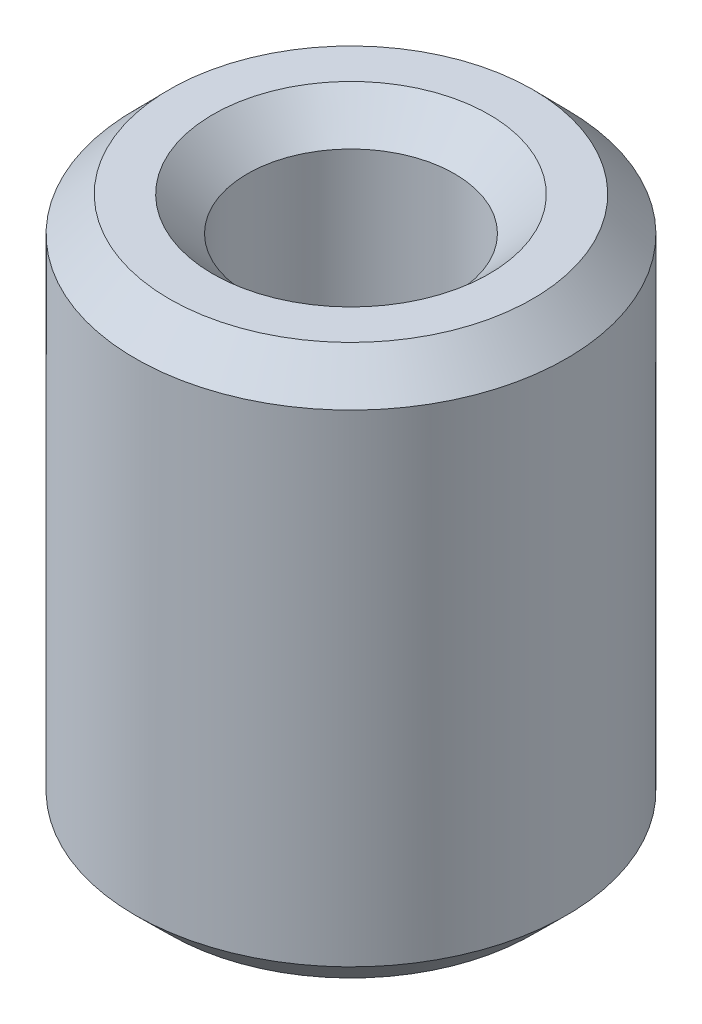
SolidWorks part; units mm, degrees
ref_plane "Front Plane" through (0, 0, 0) normal (0, 0, 1) x (1, 0, 0)
ref_plane "Top Plane" through (0, 0, 0) normal (0, 1, 0) x (1, 0, 0)
ref_plane "Right Plane" through (0, 0, 0) normal (1, 0, 0) x (0, 0, -1)
sketch "Sketch1" plane through (0, 0, 0) normal (0, 1, 0) x (1, 0, 0)
  circle A0 centre (0, 0) radius 7.5
  dimension "SLEEVE_OD" = 15
extrude "Boss-Extrude1" add sketch "Sketch1" along normal blind 19.1575
sketch "Sketch2" plane through (0, 0, 0) normal (0, 1, 0) x (1, 0, 0)
  circle A0 centre (0, 0) radius 3.6037
  dimension "BORE_D" = 7.2074
extrude "Cut-Extrude1" cut sketch "Sketch2" along normal through all
chamfer "Chamfer1" distance 1.2011 angle 44.607 4 edges at (0, 19.1575, 3.6037) (0, 0, 3.6037) (0, 0, 7.5) (0, 19.1575, 7.5) first distance on face at (0, 19.1575, 3.6037) first distance on face at (0, 0, 3.6037) first distance on face at (0, 19.1575, 7.5)
